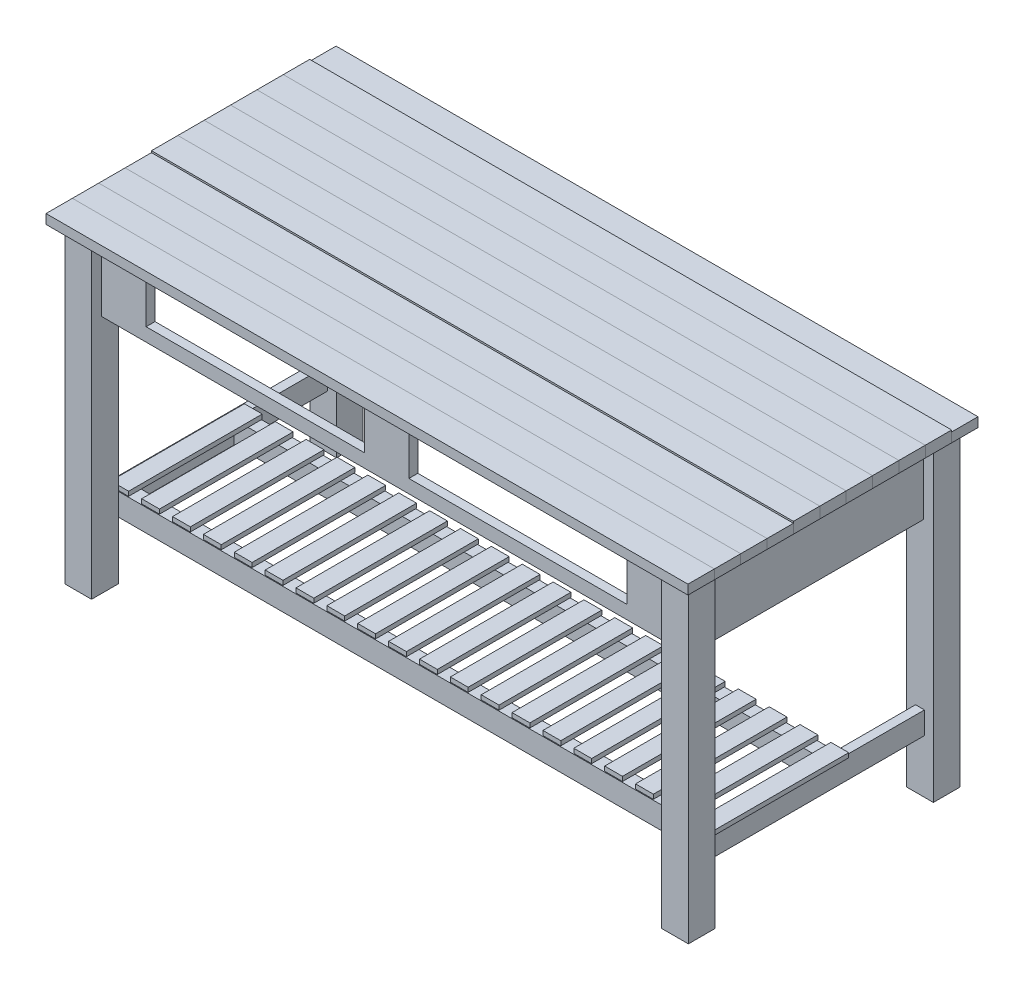
SolidWorks part; units mm, degrees
ref_plane "Default Plane" through (914.4, 26.9875, 137.455) normal (0, -1, 0) x (-1, 0, 0)
sketch3d "Bounding-Box_Cut-List-Item1"
  line L0 (0, 75.184, 0) -> (1830.3875, 75.184, 0) construction
  line L1 (1830.3875, 75.184, 0) -> (1830.3875, 0, 0) construction
  line L2 (1830.3875, 0, 0) -> (0, 0, 0) construction
  line L3 (0, 0, 0) -> (0, 75.184, 0) construction
  line L4 (0, 75.184, 26.9875) -> (1830.3875, 75.184, 26.9875) construction
  line L5 (1830.3875, 75.184, 26.9875) -> (1830.3875, 0, 26.9875) construction
  line L6 (1830.3875, 0, 26.9875) -> (0, 0, 26.9875) construction
  line L7 (0, 0, 26.9875) -> (0, 75.184, 26.9875) construction
  line L8 (0, 75.184, 0) -> (0, 75.184, 26.9875) construction
  line L9 (1830.3875, 75.184, 0) -> (1830.3875, 75.184, 26.9875) construction
  line L10 (1830.3875, 0, 0) -> (1830.3875, 0, 26.9875) construction
  line L11 (0, 0, 0) -> (0, 0, 26.9875) construction
ref_plane "Default Plane" through (889, 0, -663.915) normal (-1, 0, 0) x (0, 0, 1)
sketch3d "Bounding-Box_Cut-List-Item4"
  line L0 (76.2, 0, 0) -> (76.2, -887.4125, 0) construction
  line L1 (76.2, -887.4125, 0) -> (0, -887.4125, 0) construction
  line L2 (0, -887.4125, 0) -> (0, 0, 0) construction
  line L3 (0, 0, 0) -> (76.2, 0, 0) construction
  line L4 (76.2, 0, 76.2) -> (76.2, -887.4125, 76.2) construction
  line L5 (76.2, -887.4125, 76.2) -> (0, -887.4125, 76.2) construction
  line L6 (0, -887.4125, 76.2) -> (0, 0, 76.2) construction
  line L7 (0, 0, 76.2) -> (76.2, 0, 76.2) construction
  line L8 (76.2, 0, 0) -> (76.2, 0, 76.2) construction
  line L9 (76.2, -887.4125, 0) -> (76.2, -887.4125, 76.2) construction
  line L10 (0, -887.4125, 0) -> (0, -887.4125, 76.2) construction
  line L11 (0, 0, 0) -> (0, 0, 76.2) construction
ref_plane "Default Plane" through (863.6, -671.5125, -587.715) normal (-1, 0, 0) x (0, 0, 1)
sketch3d "Bounding-Box_Cut-List-Item5"
  line L0 (0, -63.5, 0) -> (622.3, -63.5, 0) construction
  line L1 (622.3, -63.5, 0) -> (622.3, 0, 0) construction
  line L2 (622.3, 0, 0) -> (0, 0, 0) construction
  line L3 (0, 0, 0) -> (0, -63.5, 0) construction
  line L4 (0, -63.5, 25.4) -> (622.3, -63.5, 25.4) construction
  line L5 (622.3, -63.5, 25.4) -> (622.3, 0, 25.4) construction
  line L6 (622.3, 0, 25.4) -> (0, 0, 25.4) construction
  line L7 (0, 0, 25.4) -> (0, -63.5, 25.4) construction
  line L8 (0, -63.5, 0) -> (0, -63.5, 25.4) construction
  line L9 (622.3, -63.5, 0) -> (622.3, -63.5, 25.4) construction
  line L10 (622.3, 0, 0) -> (622.3, 0, 25.4) construction
  line L11 (0, 0, 0) -> (0, 0, 25.4) construction
ref_plane "Default Plane" through (-812.8, 0, -663.915) normal (-1, 0, 0) x (0, 0, 1)
sketch3d "Bounding-Box_Cut-List-Item6"
  line L0 (0, 0, 0) -> (0, -887.4125, 0) construction
  line L1 (0, -887.4125, 0) -> (774.7, -887.4125, 0) construction
  line L2 (774.7, -887.4125, 0) -> (774.7, 0, 0) construction
  line L3 (774.7, 0, 0) -> (0, 0, 0) construction
  line L4 (0, 0, 76.2) -> (0, -887.4125, 76.2) construction
  line L5 (0, -887.4125, 76.2) -> (774.7, -887.4125, 76.2) construction
  line L6 (774.7, -887.4125, 76.2) -> (774.7, 0, 76.2) construction
  line L7 (774.7, 0, 76.2) -> (0, 0, 76.2) construction
  line L8 (0, 0, 0) -> (0, 0, 76.2) construction
  line L9 (0, -887.4125, 0) -> (0, -887.4125, 76.2) construction
  line L10 (774.7, -887.4125, 0) -> (774.7, -887.4125, 76.2) construction
  line L11 (774.7, 0, 0) -> (774.7, 0, 76.2) construction
material "Beech"
ref_plane "Front Plane" through (0, 0, 0) normal (0, 0, 1) x (1, 0, 0)
ref_plane "Top Plane" through (0, 0, 0) normal (0, 1, 0) x (1, 0, 0)
ref_plane "Right Plane" through (0, 0, 0) normal (1, 0, 0) x (0, 0, -1)
sketch "Sketch1" plane through (0, 0, 0) normal (0, 1, 0) x (1, 0, 0)
  line L0 (0, -450.3596) -> (0, 450.3596) construction
  line L1 (-915.9875, -62.271) -> (914.4, -62.271)
  line L2 (-915.9875, -62.271) -> (-915.9875, -137.455)
  line L3 (-915.9875, -137.455) -> (914.4, -137.455)
  line L4 (914.4, -62.271) -> (914.4, -137.455)
  line L6 (-915.9875, -62.271) -> (914.4, -62.271)
  line L7 (-915.9875, -62.271) -> (-915.9875, 12.913)
  line L8 (-915.9875, 12.913) -> (914.4, 12.913)
  line L9 (914.4, -62.271) -> (914.4, 12.913)
  line L10 (-915.9875, 12.913) -> (914.4, 12.913)
  line L11 (-915.9875, 12.913) -> (-915.9875, 88.097)
  line L12 (-915.9875, 88.097) -> (914.4, 88.097)
  line L13 (914.4, 12.913) -> (914.4, 88.097)
  line L14 (-915.9875, 88.097) -> (914.4, 88.097)
  line L15 (-915.9875, 88.097) -> (-915.9875, 163.281)
  line L16 (-915.9875, 163.281) -> (914.4, 163.281)
  line L17 (914.4, 88.097) -> (914.4, 163.281)
  line L18 (-915.9875, 163.281) -> (914.4, 163.281)
  line L19 (-915.9875, 163.281) -> (-915.9875, 238.465)
  line L20 (-915.9875, 238.465) -> (914.4, 238.465)
  line L21 (914.4, 163.281) -> (914.4, 238.465)
  line L22 (-915.9875, 238.465) -> (914.4, 238.465)
  line L23 (-915.9875, 238.465) -> (-915.9875, 313.649)
  line L24 (-915.9875, 313.649) -> (914.4, 313.649)
  line L25 (914.4, 238.465) -> (914.4, 313.649)
  line L26 (-915.9875, 313.649) -> (914.4, 313.649)
  line L27 (-915.9875, 313.649) -> (-915.9875, 388.833)
  line L28 (-915.9875, 388.833) -> (914.4, 388.833)
  line L29 (914.4, 313.649) -> (914.4, 388.833)
  line L30 (-915.9875, 388.833) -> (914.4, 388.833)
  line L31 (-915.9875, 388.833) -> (-915.9875, 464.017)
  line L32 (-915.9875, 464.017) -> (914.4, 464.017)
  line L33 (914.4, 388.833) -> (914.4, 464.017)
  line L34 (-915.9875, 464.017) -> (914.4, 464.017)
  line L35 (-915.9875, 464.017) -> (-915.9875, 539.201)
  line L36 (-915.9875, 539.201) -> (914.4, 539.201)
  line L37 (914.4, 464.017) -> (914.4, 539.201)
  line L38 (-915.9875, 539.201) -> (914.4, 539.201)
  line L39 (-915.9875, 539.201) -> (-915.9875, 614.385)
  line L40 (-915.9875, 614.385) -> (914.4, 614.385)
  line L41 (914.4, 539.201) -> (914.4, 614.385)
  line L42 (-915.9875, 614.385) -> (914.4, 614.385)
  line L44 (-915.9875, 614.385) -> (914.4, 614.385)
  line L46 (914.4, -137.455) -> (-915.9875, -137.455)
  line L47 (-915.9875, 614.385) -> (914.4, 614.385)
  line L48 (-915.9875, 614.385) -> (-915.9875, 689.569)
  line L49 (-915.9875, 689.569) -> (914.4, 689.569)
  line L50 (914.4, 614.385) -> (914.4, 689.569)
  dimension "D1" = 75.184
  dimension "D2" = 1830.3875
  dimension "D3" = 914.4
  dimension "D4" = 75.184
extrude "top1" add sketch "Sketch1" along normal blind 26.9875 contours L4 L1 L2 L3 region at (-0.7938, 0, 99.863)
extrude "top2" add sketch "Sketch1<9>" along normal blind 26.924 separate body contours L1 L9 L8 L7 region at (-0.7938, 0, 24.679)
sketch "Sketch1<9>" plane through (0, 0, 0) normal (0, 1, 0) x (1, 0, 0) same geometry as "Sketch1"
extrude "top3" add sketch "Sketch1<10>" along normal blind 26.924 separate body contours L8 L13 L12 L11 region at (-0.7938, 0, -50.505)
sketch "Sketch1<10>" plane through (0, 0, 0) normal (0, 1, 0) x (1, 0, 0) same geometry as "Sketch1"
extrude "top4" add sketch "Sketch1<11>" along normal blind 26.924 separate body contours L12 L17 L16 L15 region at (-0.7938, 0, -125.689)
sketch "Sketch1<11>" plane through (0, 0, 0) normal (0, 1, 0) x (1, 0, 0) same geometry as "Sketch1"
extrude "top5" add sketch "Sketch1<12>" along normal blind 31.75 separate body contours L16 L21 L20 L19 region at (-0.7938, 0, -200.873)
sketch "Sketch1<12>" plane through (0, 0, 0) normal (0, 1, 0) x (1, 0, 0) same geometry as "Sketch1"
extrude "top6" add sketch "Sketch1<13>" along normal blind 31.75 separate body contours L20 L25 L24 L23 region at (-0.7938, 0, -276.057)
sketch "Sketch1<13>" plane through (0, 0, 0) normal (0, 1, 0) x (1, 0, 0) same geometry as "Sketch1"
extrude "top7" add sketch "Sketch1<14>" along normal blind 31.75 separate body contours L24 L29 L28 L27 region at (-0.7938, 0, -351.241)
sketch "Sketch1<14>" plane through (0, 0, 0) normal (0, 1, 0) x (1, 0, 0) same geometry as "Sketch1"
extrude "top8" add sketch "Sketch1<15>" along normal blind 31.75 separate body contours L28 L33 L32 L31 region at (-0.7938, 0, -426.425)
sketch "Sketch1<15>" plane through (0, 0, 0) normal (0, 1, 0) x (1, 0, 0) same geometry as "Sketch1"
extrude "top9" add sketch "Sketch1<16>" along normal blind 31.75 separate body contours L32 L37 L36 L35 region at (-0.7938, 0, -501.609)
sketch "Sketch1<16>" plane through (0, 0, 0) normal (0, 1, 0) x (1, 0, 0) same geometry as "Sketch1"
extrude "top10" add sketch "Sketch1<17>" along normal blind 31.75 separate body contours L36 L41 L40 L39 region at (-0.7938, 0, -576.793)
sketch "Sketch1<17>" plane through (0, 0, 0) normal (0, 1, 0) x (1, 0, 0) same geometry as "Sketch1"
extrude "top11" add sketch "Sketch1<20>" along normal blind 26.924 separate body contours L3 L49 region at (-0.7938, 0, -651.977)
sketch "Sketch1<20>" plane through (0, 0, 0) normal (0, 1, 0) x (1, 0, 0) same geometry as "Sketch1"
sketch "Sketch2" plane through (0, 0, 0) normal (0, 1, 0) x (1, 0, 0)
  line L1 (-889, -110.785) -> (-812.8, -110.785)
  line L2 (-889, -110.785) -> (-889, -34.585)
  line L3 (-889, -34.585) -> (-812.8, -34.585)
  line L4 (-812.8, -110.785) -> (-812.8, -34.585)
  line L5 (-889, 587.715) -> (-812.8, 587.715)
  line L6 (-889, 587.715) -> (-889, 663.915)
  line L7 (-889, 663.915) -> (-812.8, 663.915)
  line L8 (-812.8, 587.715) -> (-812.8, 663.915)
  line L10 (0, -1000) -> (0, 49000) construction
  line L11 (812.8, 587.715) -> (812.8, 663.915)
  line L12 (889, 663.915) -> (812.8, 663.915)
  line L13 (889, 587.715) -> (889, 663.915)
  line L14 (889, 587.715) -> (812.8, 587.715)
  line L15 (812.8, -110.785) -> (812.8, -34.585)
  line L16 (889, -34.585) -> (812.8, -34.585)
  line L17 (889, -110.785) -> (889, -34.585)
  line L18 (889, -110.785) -> (812.8, -110.785)
  dimension "D1" = 76.2
  dimension "D2" = 76.2
  dimension "D3" = 622.3
  dimension "D4" = 812.8
  dimension "D5" = 812.8
extrude "table legs" add sketch "Sketch2" against normal blind 887.4125 separate body
ref_plane "Plane6" through (0, 0, -587.715) normal (0, 0, 1) x (1, 0, 0)
sketch "Sketch4" plane through (0, 0, -587.715) normal (0, 0, 1) x (1, 0, 0)
  line L0 (812.8, -887.4125) -> (889, -887.4125) construction
  line L1 (838.2, -671.5125) -> (863.6, -671.5125)
  line L2 (838.2, -671.5125) -> (838.2, -735.0125)
  line L3 (838.2, -735.0125) -> (863.6, -735.0125)
  line L4 (863.6, -671.5125) -> (863.6, -735.0125)
  line L5 (812.8, -887.4125) -> (812.8, 0) construction
  line L6 (889, -887.4125) -> (889, 0) construction
  point P4 (850.9, -887.4125)
  dimension "D1" = 152.4
  dimension "D2" = 25.4
  dimension "D3" = 63.5
  dimension "D4" = 25.4
extrude "stretcher width" add sketch "Sketch4" along normal up to surface (622.3 mm away) separate body up to face at (850.9, -443.7062, 34.585)
mirror "Mirror4" about plane through (0, 0, 0) normal (1, 0, 0) of "stretcher width"
ref_plane "Plane7" through (-838.2, 0, 0) normal (1, 0, 0) x (0, 0, -1)
sketch "Sketch5" plane through (-838.2, 0, 0) normal (1, 0, 0) x (0, 0, -1)
  line L1 (-34.585, -671.5125) -> (587.715, -671.5125) construction
  line L2 (-21.885, -671.5125) -> (16.215, -671.5125)
  line L3 (-21.885, -671.5125) -> (-21.885, -735.0125)
  line L4 (-21.885, -735.0125) -> (16.215, -735.0125)
  line L5 (16.215, -671.5125) -> (16.215, -735.0125)
  line L6 (-34.585, -735.0125) -> (587.715, -735.0125) construction
  line L7 (-34.585, -887.4125) -> (-34.585, 0) construction
  line L8 (587.715, -671.5125) -> (587.715, -735.0125) construction
  line L9 (359.115, -671.5125) -> (321.015, -671.5125)
  line L10 (359.115, -671.5125) -> (359.115, -735.0125)
  line L11 (359.115, -735.0125) -> (321.015, -735.0125)
  line L12 (321.015, -671.5125) -> (321.015, -735.0125)
  dimension "D1" = 12.7
  dimension "D2" = 38.1
  dimension "D3" = 228.6
  dimension "D4" = 38.1
extrude "stretcher length" add sketch "Sketch5" along normal up to surface (1676.4 mm away) separate body up to face at (838.2, -703.2625, -276.565)
ref_plane "Plane9" through (-812.8, 0, 0) normal (1, 0, 0) x (0, 0, -1)
sketch "Sketch7" plane through (-812.8, 0, 0) normal (1, 0, 0) x (0, 0, -1)
  line L0 (-110.785, 0) -> (-34.585, 0) construction
  line L1 (-82.21, 0) -> (-56.81, 0)
  line L2 (-82.21, 0) -> (-82.21, -203.2)
  line L3 (-82.21, -203.2) -> (-56.81, -203.2)
  line L4 (-56.81, 0) -> (-56.81, -203.2)
  line L6 (-34.585, -887.4125) -> (-34.585, 0) construction
  dimension "D1" = 22.225
  dimension "D2" = 25.4
  dimension "D3" = 203.2
extrude "front face plate" add sketch "Sketch7" along normal up to surface (1625.6 mm away) separate body up to face at (812.8, -443.7062, 72.685)
sketch "Sketch8" plane through (0, 0, -587.715) normal (0, 0, 1) x (1, 0, 0)
  line L0 (812.8, 0) -> (889, 0) construction
  line L1 (860.425, 0) -> (835.025, 0)
  line L2 (860.425, 0) -> (860.425, -203.2)
  line L3 (860.425, -203.2) -> (835.025, -203.2)
  line L4 (835.025, 0) -> (835.025, -203.2)
  line L6 (-889, 0) -> (-812.8, 0) construction
  line L7 (-860.425, 0) -> (-835.025, 0)
  line L8 (-860.425, 0) -> (-860.425, -203.2)
  line L9 (-860.425, -203.2) -> (-835.025, -203.2)
  line L10 (-835.025, 0) -> (-835.025, -203.2)
  line L12 (-812.8, -887.4125) -> (-812.8, 0) construction
  line L13 (812.8, -887.4125) -> (812.8, 0) construction
  dimension "D1" = 22.225
  dimension "D2" = 25.4
  dimension "D3" = 203.2
  dimension "D4" = 22.225
  dimension "D5" = 25.4
  dimension "D6" = 203.2
extrude "side face plates" add sketch "Sketch8" along normal up to surface (622.3 mm away) separate body up to face at (-850.9, -443.7062, 34.585)
ref_plane "Plane10" through (0, 0, -359.115) normal (0, 0, -1) x (-1, 0, 0)
sketch "Sketch9" plane through (0, 0, -359.115) normal (0, 0, -1) x (-1, 0, 0)
  line L0 (-788.2167, -669.1659) -> (-737.4167, -669.1659)
  line L1 (-876.2277, -669.1659) -> (-825.4277, -669.1659)
  line L2 (-876.2277, -669.1659) -> (-876.2277, -656.4659)
  line L3 (-876.2277, -656.4659) -> (-825.4277, -656.4659)
  line L4 (-825.4277, -669.1659) -> (-825.4277, -656.4659)
  line L5 (-788.2167, -669.1659) -> (-788.2167, -656.4659)
  line L6 (-788.2167, -656.4659) -> (-737.4167, -656.4659)
  line L7 (-737.4167, -669.1659) -> (-737.4167, -656.4659)
  line L8 (-700.2057, -669.1659) -> (-649.4057, -669.1659)
  line L9 (-700.2057, -669.1659) -> (-700.2057, -656.4659)
  line L10 (-700.2057, -656.4659) -> (-649.4057, -656.4659)
  line L11 (-649.4057, -669.1659) -> (-649.4057, -656.4659)
  line L12 (-612.1947, -669.1659) -> (-561.3947, -669.1659)
  line L13 (-612.1947, -669.1659) -> (-612.1947, -656.4659)
  line L14 (-612.1947, -656.4659) -> (-561.3947, -656.4659)
  line L15 (-561.3947, -669.1659) -> (-561.3947, -656.4659)
  line L16 (-524.1837, -669.1659) -> (-473.3837, -669.1659)
  line L17 (-524.1837, -669.1659) -> (-524.1837, -656.4659)
  line L18 (-524.1837, -656.4659) -> (-473.3837, -656.4659)
  line L19 (-473.3837, -669.1659) -> (-473.3837, -656.4659)
  line L20 (-436.1727, -669.1659) -> (-385.3727, -669.1659)
  line L21 (-436.1727, -669.1659) -> (-436.1727, -656.4659)
  line L22 (-436.1727, -656.4659) -> (-385.3727, -656.4659)
  line L23 (-385.3727, -669.1659) -> (-385.3727, -656.4659)
  line L24 (-348.1617, -669.1659) -> (-297.3617, -669.1659)
  line L25 (-348.1617, -669.1659) -> (-348.1617, -656.4659)
  line L26 (-348.1617, -656.4659) -> (-297.3617, -656.4659)
  line L27 (-297.3617, -669.1659) -> (-297.3617, -656.4659)
  line L28 (-260.1507, -669.1659) -> (-209.3507, -669.1659)
  line L29 (-260.1507, -669.1659) -> (-260.1507, -656.4659)
  line L30 (-260.1507, -656.4659) -> (-209.3507, -656.4659)
  line L31 (-209.3507, -669.1659) -> (-209.3507, -656.4659)
  line L32 (-172.1397, -669.1659) -> (-121.3397, -669.1659)
  line L33 (-172.1397, -669.1659) -> (-172.1397, -656.4659)
  line L34 (-172.1397, -656.4659) -> (-121.3397, -656.4659)
  line L35 (-121.3397, -669.1659) -> (-121.3397, -656.4659)
  line L36 (-84.1287, -669.1659) -> (-33.3287, -669.1659)
  line L37 (-84.1287, -669.1659) -> (-84.1287, -656.4659)
  line L38 (-84.1287, -656.4659) -> (-33.3287, -656.4659)
  line L39 (-33.3287, -669.1659) -> (-33.3287, -656.4659)
  line L40 (3.8823, -669.1659) -> (54.6823, -669.1659)
  line L41 (3.8823, -669.1659) -> (3.8823, -656.4659)
  line L42 (3.8823, -656.4659) -> (54.6823, -656.4659)
  line L43 (54.6823, -669.1659) -> (54.6823, -656.4659)
  line L44 (91.8933, -669.1659) -> (142.6933, -669.1659)
  line L45 (91.8933, -669.1659) -> (91.8933, -656.4659)
  line L46 (91.8933, -656.4659) -> (142.6933, -656.4659)
  line L47 (142.6933, -669.1659) -> (142.6933, -656.4659)
  line L48 (179.9043, -669.1659) -> (230.7043, -669.1659)
  line L49 (179.9043, -669.1659) -> (179.9043, -656.4659)
  line L50 (179.9043, -656.4659) -> (230.7043, -656.4659)
  line L51 (230.7043, -669.1659) -> (230.7043, -656.4659)
  line L52 (267.9153, -669.1659) -> (318.7153, -669.1659)
  line L53 (267.9153, -669.1659) -> (267.9153, -656.4659)
  line L54 (267.9153, -656.4659) -> (318.7153, -656.4659)
  line L55 (318.7153, -669.1659) -> (318.7153, -656.4659)
  line L56 (355.9263, -669.1659) -> (406.7263, -669.1659)
  line L57 (355.9263, -669.1659) -> (355.9263, -656.4659)
  line L58 (355.9263, -656.4659) -> (406.7263, -656.4659)
  line L59 (406.7263, -669.1659) -> (406.7263, -656.4659)
  line L60 (443.9373, -669.1659) -> (494.7373, -669.1659)
  line L61 (443.9373, -669.1659) -> (443.9373, -656.4659)
  line L62 (443.9373, -656.4659) -> (494.7373, -656.4659)
  line L63 (494.7373, -669.1659) -> (494.7373, -656.4659)
  line L64 (531.9483, -669.1659) -> (582.7483, -669.1659)
  line L65 (531.9483, -669.1659) -> (531.9483, -656.4659)
  line L66 (531.9483, -656.4659) -> (582.7483, -656.4659)
  line L67 (582.7483, -669.1659) -> (582.7483, -656.4659)
  line L68 (619.9593, -669.1659) -> (670.7593, -669.1659)
  line L69 (619.9593, -669.1659) -> (619.9593, -656.4659)
  line L70 (619.9593, -656.4659) -> (670.7593, -656.4659)
  line L71 (670.7593, -669.1659) -> (670.7593, -656.4659)
  line L72 (707.9703, -669.1659) -> (758.7703, -669.1659)
  line L73 (707.9703, -669.1659) -> (707.9703, -656.4659)
  line L74 (707.9703, -656.4659) -> (758.7703, -656.4659)
  line L75 (758.7703, -669.1659) -> (758.7703, -656.4659)
  line L76 (795.9813, -669.1659) -> (846.7813, -669.1659)
  line L77 (795.9813, -669.1659) -> (795.9813, -656.4659)
  line L78 (795.9813, -656.4659) -> (846.7813, -656.4659)
  line L79 (846.7813, -669.1659) -> (846.7813, -656.4659)
  dimension "D1" = 38.1
  dimension "D2" = 50.8
  dimension "D3" = 12.7
  dimension "D4" = 20
extrude "stretcher rack boards" add sketch "Sketch9" against normal up to surface (381 mm away) separate body up to face at (0, -703.2625, 21.885)
ref_plane "Plane11" through (0, 0, 82.21) normal (0, 0, 1) x (1, 0, 0)
sketch "Sketch10" plane through (0, 0, 82.21) normal (0, 0, 1) x (1, 0, 0)
  line L0 (-812.8, 0) -> (-812.8, -203.2) construction
  line L1 (-685.8, -38.1) -> (-63.5, -38.1)
  line L2 (-685.8, -38.1) -> (-685.8, -165.1)
  line L3 (-685.8, -165.1) -> (-63.5, -165.1)
  line L4 (-63.5, -38.1) -> (-63.5, -165.1)
  line L5 (812.8, 0) -> (-812.8, 0) construction
  line L6 (812.8, -203.2) -> (-812.8, -203.2) construction
  line L7 (63.5, -38.1) -> (685.8, -38.1)
  line L8 (63.5, -38.1) -> (63.5, -165.1)
  line L9 (63.5, -165.1) -> (685.8, -165.1)
  line L10 (685.8, -38.1) -> (685.8, -165.1)
  dimension "D1" = 127
  dimension "D2" = 38.1
  dimension "D3" = 38.1
  dimension "D4" = 622.3
  dimension "D5" = 2
  dimension "D6" = 127
extrude "drawer cut outs" cut sketch "Sketch10" against normal up to next (25.4 mm away)
ref_plane "Plane12" through (-812.8, 0, 0) normal (1, 0, 0) x (0, 0, -1)
sketch "Sketch11" plane through (-812.8, 0, 0) normal (1, 0, 0) x (0, 0, -1)
  line L0 (587.715, 0) -> (663.915, 0) construction
  line L1 (635.34, 0) -> (609.94, 0)
  line L2 (635.34, 0) -> (635.34, -101.6)
  line L3 (635.34, -101.6) -> (609.94, -101.6)
  line L4 (609.94, 0) -> (609.94, -101.6)
  line L6 (587.715, -887.4125) -> (587.715, 0) construction
  dimension "D1" = 22.225
  dimension "D2" = 101.6
  dimension "D3" = 25.4
extrude "back face plate" add sketch "Sketch11" along normal up to surface (1625.6 mm away) separate body up to face at (812.8, -443.7062, -625.815)
equation "\"table_thickness\"= \" 1 1 / 16\"in"
equation "\"D1@top1\"=\"table_thickness\""
equation "\"D1@top3\"=1.0625"
equation "\"D1@top4\"=1.0625"
equation "\"D1@top5\"=\"table_thickness\""
equation "\"D1@top6\"=\"table_thickness\""
equation "\"D1@top7\"=\"table_thickness\""
equation "\"D1@top8\"=\"table_thickness\""
equation "\"D1@top9\"=\"table_thickness\""
equation "\"D1@top10\"=\"table_thickness\""
equation "\"D1@top11\"=1.0625"
